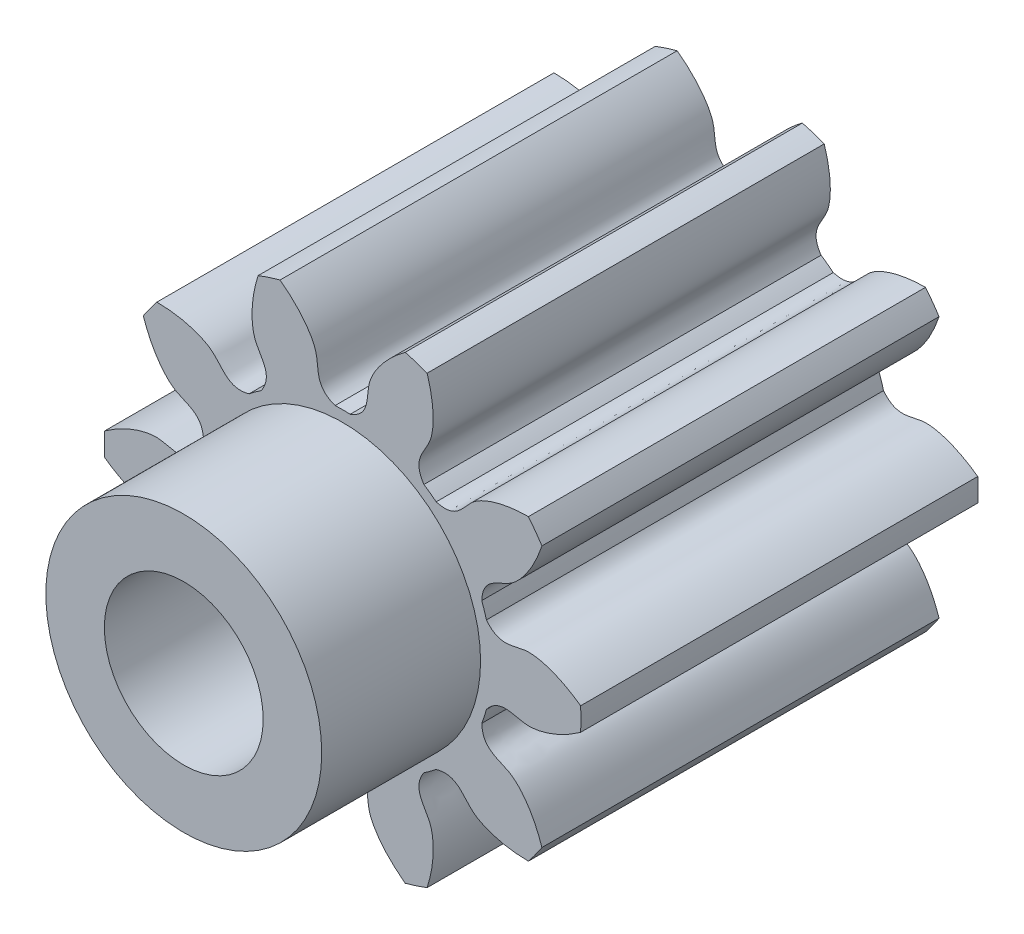
SolidWorks part; units mm, degrees
ref_plane "前视基准面" through (0, 0, 0) normal (0, 0, 1) x (1, 0, 0)
ref_plane "上视基准面" through (0, 0, 0) normal (0, 1, 0) x (1, 0, 0)
ref_plane "右视基准面" through (0, 0, 0) normal (1, 0, 0) x (0, 0, -1)
sketch "草图1" plane through (0, 0, 0) normal (0, 0, 1) x (1, 0, 0)
  circle A0 centre (0, 0) radius 3
extrude "凸台-拉伸1" add sketch "草图1" along normal blind 5
ref_axis "基准轴1" through (0, 0, -0.3) along (0, 0, 1)
sketch "草图2" plane through (0, 0, 0) normal (0, 0, 1) x (1, 0, 0)
  line L0 (0, 0) -> (0, 3) construction
  circle A0 centre (0, 0) radius 3 construction
  arc A1 (0.0952, 1.8726) -> (-0.0952, 1.8726) centre (0, 0) ccw
  arc A2 (2.1268, 3.3471) -> (-2.1268, 3.3471) centre (0, 0) ccw
  spline S0 degree 3 poles (0.0952, 1.8726) (0.3627, 1.9703) (0.2869, 2.1853) (0.3443, 2.3623) (0.3473, 2.3708) (0.3507, 2.38) (0.3546, 2.3901) (0.3591, 2.4009) (0.3642, 2.4126) (0.3699, 2.4249) (0.3763, 2.438) (0.3834, 2.4518) (0.3911, 2.4663) (0.3997, 2.4815) (0.409, 2.4972) (0.4191, 2.5136) (0.4301, 2.5306) (0.4419, 2.5481) (0.4546, 2.5662) (0.4682, 2.5848) (0.4828, 2.6038) (0.4983, 2.6233) (0.5148, 2.6432) (0.5323, 2.6634) (0.5509, 2.684) (0.5705, 2.7049) (0.5911, 2.7261) (0.6129, 2.7476) (0.6358, 2.7692) (0.6598, 2.791) (0.6849, 2.8129) (0.7112, 2.835) (0.7386, 2.8571) (0.7672, 2.8792) (0.7971, 2.9013) (0.8281, 2.9234) (0.8603, 2.9453) (0.8938, 2.9671) (0.9285, 2.9888) (0.9644, 3.0102) (1.0015, 3.0314) (1.0399, 3.0522) (1.0796, 3.0728) (1.1204, 3.0929) (1.1626, 3.1126) (1.2059, 3.1319) (1.2506, 3.1506) (1.2964, 3.1688) (1.3435, 3.1864) (1.3918, 3.2034) (1.4414, 3.2197) (1.4921, 3.2353) (1.5441, 3.2501) (1.5972, 3.2642) (1.6516, 3.2773) (1.7071, 3.2896) (1.7638, 3.301) (1.8216, 3.3114) (1.8805, 3.3208) (1.9405, 3.3291) (2.0227, 3.3388) (2.0849, 3.3443) (2.1268, 3.3471) knots 0 0 0 0 0.201721 0.204697 0.208023 0.211699 0.215726 0.220102 0.224829 0.229906 0.235332 0.241109 0.247237 0.253714 0.260541 0.267719 0.275246 0.283124 0.291352 0.29993 0.308858 0.318136 0.327765 0.337743 0.348072 0.358751 0.36978 0.381158 0.392888 0.404967 0.417396 0.430176 0.443305 0.456785 0.470615 0.484795 0.499325 0.514205 0.529435 0.545016 0.560946 0.577227 0.593858 0.610839 0.62817 0.645851 0.663882 0.682264 0.700995 0.720077 0.739509 0.759291 0.779423 0.799905 0.820737 0.84192 0.863452 0.885335 0.907568 0.930151 0.953084 1 1 1 1
  spline S1 degree 3 poles (-0.0952, 1.8726) (-0.3627, 1.9703) (-0.2869, 2.1853) (-0.3443, 2.3623) (-0.3473, 2.3708) (-0.3507, 2.38) (-0.3546, 2.3901) (-0.3591, 2.4009) (-0.3642, 2.4126) (-0.3699, 2.4249) (-0.3763, 2.438) (-0.3834, 2.4518) (-0.3911, 2.4663) (-0.3997, 2.4815) (-0.409, 2.4972) (-0.4191, 2.5136) (-0.4301, 2.5306) (-0.4419, 2.5481) (-0.4546, 2.5662) (-0.4682, 2.5848) (-0.4828, 2.6038) (-0.4983, 2.6233) (-0.5148, 2.6432) (-0.5323, 2.6634) (-0.5509, 2.684) (-0.5705, 2.7049) (-0.5911, 2.7261) (-0.6129, 2.7476) (-0.6358, 2.7692) (-0.6598, 2.791) (-0.6849, 2.8129) (-0.7112, 2.835) (-0.7386, 2.8571) (-0.7672, 2.8792) (-0.7971, 2.9013) (-0.8281, 2.9234) (-0.8603, 2.9453) (-0.8938, 2.9671) (-0.9285, 2.9888) (-0.9644, 3.0102) (-1.0015, 3.0314) (-1.0399, 3.0522) (-1.0796, 3.0728) (-1.1204, 3.0929) (-1.1626, 3.1126) (-1.2059, 3.1319) (-1.2506, 3.1506) (-1.2964, 3.1688) (-1.3435, 3.1864) (-1.3918, 3.2034) (-1.4414, 3.2197) (-1.4921, 3.2353) (-1.5441, 3.2501) (-1.5972, 3.2642) (-1.6516, 3.2773) (-1.7071, 3.2896) (-1.7638, 3.301) (-1.8216, 3.3114) (-1.8805, 3.3208) (-1.9405, 3.3291) (-2.0227, 3.3388) (-2.0849, 3.3443) (-2.1268, 3.3471) knots 0 0 0 0 0.201721 0.204697 0.208023 0.211699 0.215726 0.220102 0.224829 0.229906 0.235332 0.241109 0.247237 0.253714 0.260541 0.267719 0.275246 0.283124 0.291352 0.29993 0.308858 0.318136 0.327765 0.337743 0.348072 0.358751 0.36978 0.381158 0.392888 0.404967 0.417396 0.430176 0.443305 0.456785 0.470615 0.484795 0.499325 0.514205 0.529435 0.545016 0.560946 0.577227 0.593858 0.610839 0.62817 0.645851 0.663882 0.682264 0.700995 0.720077 0.739509 0.759291 0.779423 0.799905 0.820737 0.84192 0.863452 0.885335 0.907568 0.930151 0.953084 1 1 1 1
extrude "切除-拉伸1" cut sketch "草图2" along normal through all
pattern_circular "阵列(圆周)1" count 10 every 36 about axis through (0, 0, -0.3) along (0, 0, 1) of "切除-拉伸1"
sketch "草图3" plane through (0, 0, 0) normal (0, 0, 1) x (1, 0, 0)
  circle A0 centre (0, 0) radius 2.5 construction
  dimension "Dn" = 5
sketch "草图4" plane through (0, 0, 0) normal (0, 0, -1) x (-1, 0, 0)
  circle A0 centre (0, 0) radius 1
  dimension "D1" = 2
extrude "切除-拉伸2" cut sketch "草图4" against normal up to next
sketch "草图5" plane through (0, 0, 5) normal (0, 0, 1) x (1, 0, 0)
  circle A0 centre (0, 0) radius 1.7368
  circle A1 centre (0, 0) radius 1 construction
  circle A2 centre (0, 0) radius 1
extrude "凸台-拉伸2" add sketch "草图5" along normal blind 2
